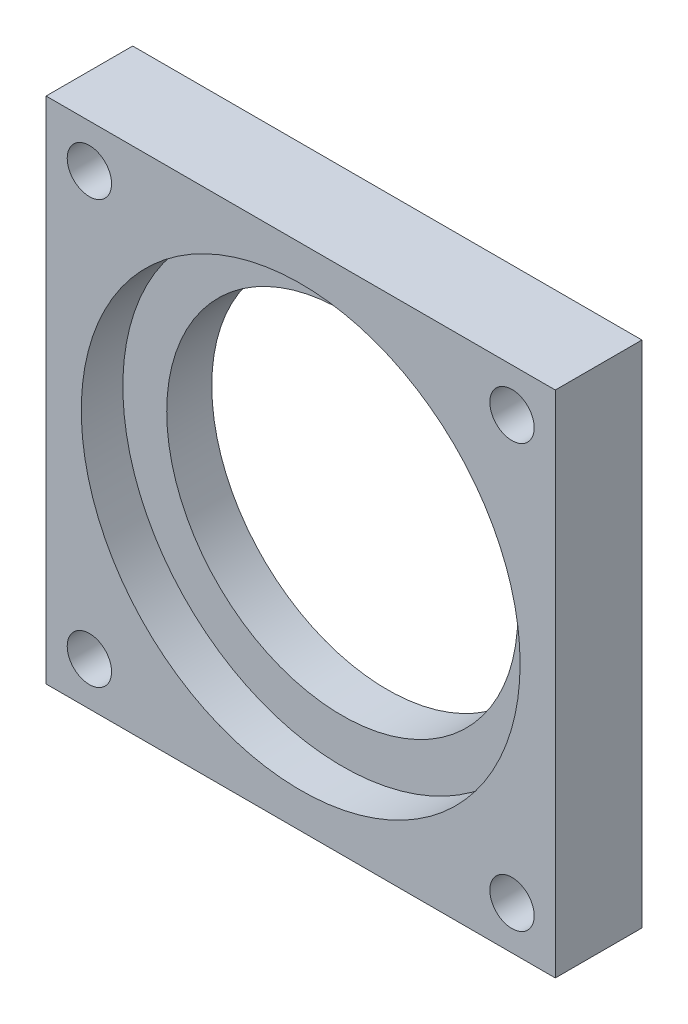
SolidWorks part; units mm, degrees
ref_plane "Front Plane" through (0, 0, 0) normal (0, 0, 1) x (1, 0, 0)
ref_plane "Top Plane" through (0, 0, 0) normal (0, 1, 0) x (1, 0, 0)
ref_plane "Right Plane" through (0, 0, 0) normal (1, 0, 0) x (0, 0, -1)
sketch "Sketch1" plane through (0, 0, 0) normal (0, 0, 1) x (1, 0, 0)
  line L1 (-14, -14) -> (14, -14)
  line L2 (-14, -14) -> (-14, 14)
  line L3 (-14, 14) -> (14, 14)
  line L4 (14, -14) -> (14, 14)
  line L5 (-14, -14) -> (14, 14) construction
  line L6 (-14, 14) -> (14, -14) construction
  point P0 (0, 0)
  dimension "D1" = 28
  dimension "D2" = 28
extrude "Boss-Extrude1" add sketch "Sketch1" along normal blind 4.7625
sketch "Sketch2" plane through (0, 0, 4.7625) normal (0, 0, 1) x (1, 0, 0)
  circle A0 centre (0, 0) radius 12.065
  dimension "D1" = 24.13
extrude "Cut-Extrude1" cut sketch "Sketch2" against normal blind 2.286
sketch "Sketch3" plane through (0, 0, 2.4765) normal (0, 0, 1) x (1, 0, 0)
  circle A0 centre (0, 0) radius 9.652
  dimension "D1" = 19.304
extrude "Cut-Extrude2" cut sketch "Sketch3" against normal through all
hole_wizard "CSK for #2 Flat Head Machine Screw1" positions "Sketch5" profile "Sketch4" countersink size "#2" standard "Ansi Inch" end condition through all
sketch "Sketch5" plane through (0, 0, 0) normal (0, 0, -1) x (-1, 0, 0)
  line L0 (14, 14) -> (14, -14) construction
  line L1 (-14, 14) -> (14, 14) construction
  line L2 (14, -14) -> (-14, -14) construction
  line L3 (-14, -14) -> (-14, 14) construction
  point P0 (11.6187, 11.6188)
  point P1 (11.6187, -11.6188)
  point P3 (-11.6187, -11.6188)
  point P5 (-11.6187, 11.6188)
  dimension "D1" = 2.3813
  dimension "D2" = 2.3813
  dimension "D3" = 2.3813
  dimension "D4" = 2.3813
sketch "Sketch4" plane through (-11.6187, 11.6188, 0) normal (1, 0, 0) x (0, 1, 0)
  line L0 (0, 0) -> (0, 4.7625)
  line L1 (0, 4.7625) -> (1.2192, 4.7625)
  line L2 (1.2192, 4.7625) -> (1.2192, 1.1103)
  line L3 (1.2192, 1.1103) -> (2.1844, 0)
  line L5 (2.1844, 0) -> (0, 0)
  line L6 (-1.2192, 1.1103) -> (-2.1844, 0) construction
  line L11 (0, -6.35) -> (0, 107.95) construction
  dimension "Thru Hole Dia." = 2.4384
  dimension "Thru Hole Depth" = 4.7625
  dimension "Near C'Sink Dia." = 4.3688
  dimension "Near C'Sink Angle" = 82
